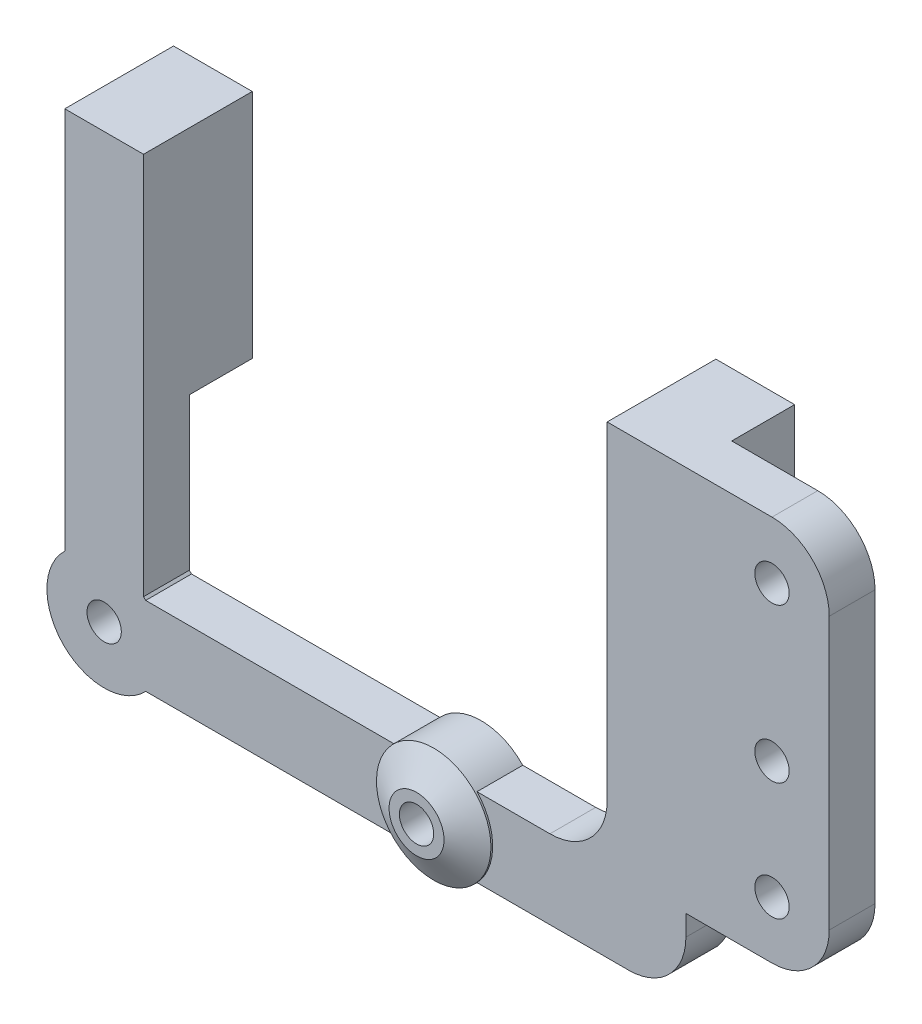
SolidWorks part; units mm, degrees
ref_plane "Alzado" through (0, 0, 0) normal (0, 0, 1) x (1, 0, 0)
ref_plane "Planta" through (0, 0, 0) normal (0, 1, 0) x (1, 0, 0)
ref_plane "Vista lateral" through (0, 0, 0) normal (1, 0, 0) x (0, 0, -1)
sketch "Croquis1" plane through (0, 0, 0) normal (0, 0, 1) x (1, 0, 0)
  line L0 (25.5, -3.4) -> (54.9, -3.4) construction
  line L1 (25.5, 10.1) -> (25.5, -16.9) construction
  line L2 (54.9, 1.74) -> (54.9, -8.54) construction
  line L3 (59.9, -8.54) -> (59.9, 15.2)
  line L4 (54.9, 20.2) -> (40.5, 20.2)
  line L8 (0, 20.2) -> (-6.88, 20.2)
  line L9 (-6.88, 20.2) -> (-6.88, -13.2714)
  line L17 (40.5, -8.46) -> (40.5, 20.2)
  line L18 (35.5, -13.46) -> (29.1286, -13.46)
  line L19 (0, 20.2) -> (0, -13.2714)
  line L20 (0.1886, -20.34) -> (21.8714, -20.34)
  line L21 (54.9, -13.54) -> (47.38, -13.54)
  line L22 (47.38, -13.54) -> (47.38, -15.34)
  line L23 (21.8714, -13.46) -> (0.1886, -13.46)
  line L24 (29.1286, -20.34) -> (42.38, -20.34)
  circle A0 centre (54.9, 1.74) radius 1.5
  circle A1 centre (54.9, -8.54) radius 1.5
  circle A2 centre (25.5, -16.9) radius 1.5
  arc A3 (21.8714, -20.34) -> (29.1286, -20.34) centre (25.5, -16.9) ccw
  arc A4 (-6.88, -13.2714) -> (0.1886, -20.34) centre (-3.44, -16.9) ccw
  arc A5 (54.9, -13.54) -> (59.9, -8.54) centre (54.9, -8.54) ccw
  arc A6 (59.9, 15.2) -> (54.9, 20.2) centre (54.9, 15.2) ccw
  arc A7 (0.1886, -13.46) -> (0, -13.2714) centre (-3.44, -16.9) ccw
  arc A8 (29.1286, -13.46) -> (21.8714, -13.46) centre (25.5, -16.9) ccw
  circle A9 centre (-3.44, -16.9) radius 1.5
  circle A10 centre (54.9, 15.2) radius 1.5
  arc A11 (35.5, -13.46) -> (40.5, -8.46) centre (35.5, -8.46) ccw
  arc A12 (42.38, -20.34) -> (47.38, -15.34) centre (42.38, -15.34) ccw
  dimension "D4" = 3
  dimension "D5" = 5
  dimension "D6" = 6.88
  dimension "D7" = 6.88
  dimension "D9" = 10
  dimension "D11" = 5
  dimension "D14" = 5
  dimension "D1" = 10.28
  dimension "D2" = 27
  dimension "D3" = 29.4
  dimension "D8" = 6.88
  dimension "D10" = 3.44
  dimension "D12" = 3.44
  dimension "D13" = 5
extrude "Saliente-Extruir1" add sketch "Croquis1" along normal blind 4
sketch "Croquis2" plane through (0, 0, 0) normal (0, 0, -1) x (-1, 0, 0)
  line L0 (-40.5, 20.2) -> (0, 20.2) construction
  line L1 (-40.5, 20.2) -> (-47.38, 20.2)
  line L2 (-40.5, 20.2) -> (-40.5, 0)
  line L3 (-40.5, 0) -> (-47.38, 0)
  line L4 (-47.38, 20.2) -> (-47.38, 0)
  line L5 (0, 0) -> (6.88, 0)
  line L6 (0, 0) -> (0, 20.2)
  line L7 (0, 20.2) -> (6.88, 20.2)
  line L8 (6.88, 0) -> (6.88, 20.2)
extrude "Saliente-Extruir2" add sketch "Croquis2" along normal up to surface (5.5 mm away)
sketch "Croquis3" plane through (0, 0, 4) normal (0, 0, 1) x (1, 0, 0)
  circle A0 centre (25.5, -16.9) radius 1.5
  circle A1 centre (25.5, -16.9) radius 5
  dimension "D1" = 3
  dimension "D2" = 10
extrude "Saliente-Extruir3" add sketch "Croquis3" along normal up to surface (1.65 mm away)
sketch "Croquis4" plane through (0, 0, 0) normal (0, 0, -1) x (-1, 0, 0)
  circle A0 centre (-25.5, -16.9) radius 1.5
  circle A1 centre (-54.9, 1.74) radius 1.5
  circle A2 centre (-54.9, -8.54) radius 1.5
  dimension "D1" = 3
extrude "Saliente-Extruir4" add sketch "Croquis4" against normal blind 1
sketch "Croquis5" plane through (0, 0, -5.5) normal (0, 0, -1) x (-1, 0, 0)
  circle A0 centre (-45.5, 5.4) radius 1.25
  circle A1 centre (-45.5, 14.8) radius 1.25
  circle A2 centre (5, 14.8) radius 1.25
  circle A3 centre (5, 5.4) radius 1.25
  dimension "D1" = 2.5
extrude "Cortar-Extruir1" cut sketch "Croquis5" against normal blind 8
chamfer "Chaflán1" distance 1.5 angle 60 1 edges at (30.5, -16.9, 5.65) first distance on face at (25.5, -16.9, 2)
